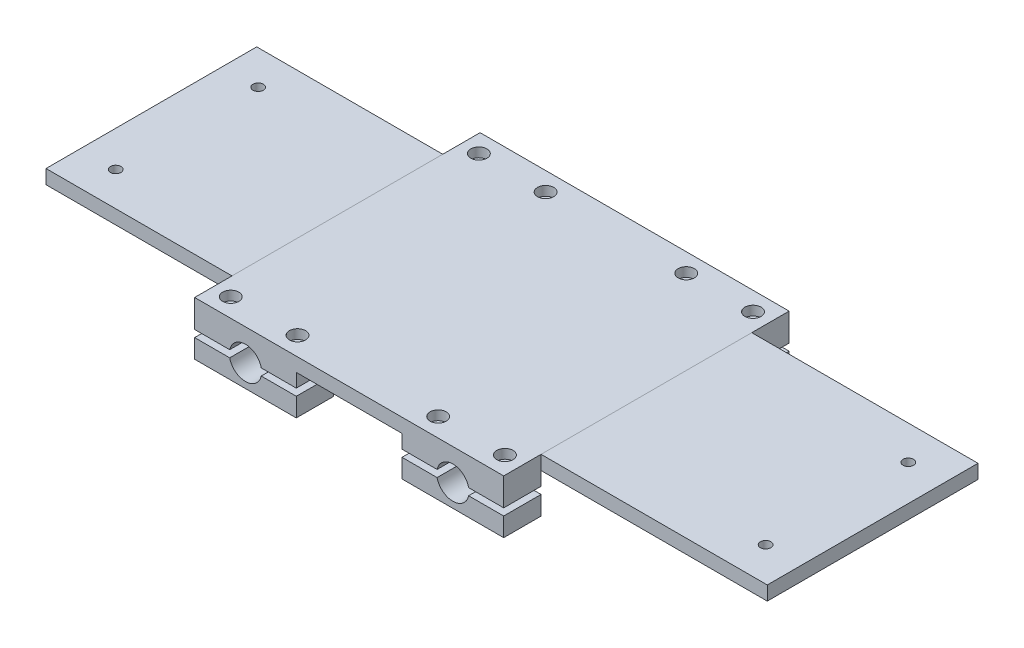
SolidWorks part; units mm, degrees
ref_plane "Front Plane" through (0, 0, 0) normal (0, 0, 1) x (1, 0, 0)
ref_plane "Top Plane" through (0, 0, 0) normal (0, 1, 0) x (1, 0, 0)
ref_plane "Right Plane" through (0, 0, 0) normal (1, 0, 0) x (0, 0, -1)
sketch "Sketch1" plane through (0, 0, 0) normal (0, 0, 1) x (1, 0, 0)
  line L0 (73.8188, 0) -> (0, 0) construction
  line L1 (-110, -15.875) -> (110, -15.875)
  line L2 (-110, -15.875) -> (-110, 15.875)
  line L3 (-110, 15.875) -> (110, 15.875)
  line L4 (110, -15.875) -> (110, 15.875)
  line L5 (-110, -15.875) -> (110, 15.875) construction
  line L6 (-110, 15.875) -> (110, -15.875) construction
  line L7 (0, 0) -> (-73.8187, 0) construction
  circle A1 centre (-73.8187, 0) radius 11.5
  circle A2 centre (73.8188, 0) radius 11.5
  point P0 (0, 0)
  dimension "D1" = 147.6375
  dimension "D4" = 23
  dimension "D2" = 31.75
  dimension "D3" = 220
extrude "Boss-Extrude1" add sketch "Sketch1" along normal blind 203.2
sketch "Sketch3" plane through (0, 0, 203.2) normal (0, 0, 1) x (1, 0, 0)
  line L0 (110, -15.875) -> (110, 15.875) construction
  line L1 (-110, 15.875) -> (110, 15.875)
  line L2 (-110, 15.875) -> (-110, 22.225)
  line L3 (-110, 22.225) -> (110, 22.225)
  line L4 (110, 15.875) -> (110, 22.225)
  dimension "D1" = 6.35
extrude "Boss-Extrude2" add sketch "Sketch3" against normal up to surface (203.2 mm away) up to face at (-62.3188, 0, 0)
sketch "Sketch4" plane through (-110, 0, 0) normal (-1, 0, 0) x (0, 0, 1)
  line L0 (203.2, -15.875) -> (0, -15.875) construction
  line L1 (26.6, -15.875) -> (176.6, -15.875)
  line L2 (26.6, -15.875) -> (26.6, 12.225)
  line L3 (26.6, 12.225) -> (176.6, 12.225)
  line L4 (176.6, -15.875) -> (176.6, 12.225)
  line L5 (0, 0) -> (26.6, 0) construction
  line L6 (26.6, 0) -> (176.6, 0) construction
  line L7 (176.6, 0) -> (203.2, 0) construction
  line L8 (203.2, 22.225) -> (203.2, -15.875) construction
  line L9 (0, 22.225) -> (203.2, 22.225) construction
  dimension "D1" = 10
  dimension "D2" = 150
extrude "Cut-Extrude1" cut sketch "Sketch4" against normal blind 253.2
sketch "Sketch5" plane through (0, 0, 0) normal (0, 0, -1) x (-1, 0, 0)
  line L0 (110, -15.875) -> (-110, -15.875) construction
  line L1 (-37.6375, -15.875) -> (37.6375, -15.875)
  line L2 (-37.6375, -15.875) -> (-37.6375, 12.225)
  line L3 (-37.6375, 12.225) -> (37.6375, 12.225)
  line L4 (37.6375, -15.875) -> (37.6375, 12.225)
  line L5 (-110, 22.225) -> (110, 22.225) construction
  line L6 (0, 0) -> (-37.6375, 0) construction
  line L7 (0, 0) -> (37.6375, 0) construction
  line L8 (-37.6375, 0) -> (-73.8188, 0) construction
  line L9 (-73.8188, 0) -> (-110, 0) construction
  line L10 (-110, -15.875) -> (-110, 22.225) construction
  dimension "D1" = 10
extrude "Cut-Extrude2" cut sketch "Sketch5" against normal blind 203.2
sketch "Sketch6" plane through (0, -15.875, 0) normal (0, -1, 0) x (1, 0, 0)
  line L0 (-110, 189.9) -> (-97.5688, 189.9) construction
  line L2 (-97.5688, 189.9) -> (-50.0688, 189.9) construction
  line L3 (-50.0688, 189.9) -> (-37.6375, 189.9) construction
  line L5 (-110, 13.3) -> (-97.5688, 13.3) construction
  line L6 (-110, 26.6) -> (-110, 0) construction
  line L7 (-97.5688, 13.3) -> (-50.0688, 13.3) construction
  line L8 (-50.0688, 13.3) -> (-37.6375, 13.3) construction
  line L9 (-37.6375, 26.6) -> (-37.6375, 0) construction
  line L10 (37.6375, 203.2) -> (37.6375, 176.6) construction
  line L11 (37.6375, 26.6) -> (37.6375, 0) construction
  line L12 (37.6375, 13.3) -> (50.0688, 13.3) construction
  line L13 (50.0688, 13.3) -> (97.5687, 13.3) construction
  line L14 (97.5687, 13.3) -> (110, 13.3) construction
  line L16 (-62.3188, 203.2) -> (-85.3187, 203.2) construction
  line L18 (110, 189.9) -> (97.5687, 189.9) construction
  line L19 (97.5687, 189.9) -> (50.0688, 189.9) construction
  line L20 (50.0688, 189.9) -> (37.6375, 189.9) construction
  line L22 (-62.3188, 203.2) -> (-85.3187, 203.2)
  line L23 (-85.3187, 203.2) -> (-85.3187, 0) construction
  line L24 (-110, 0) -> (-37.6375, 0) construction
  line L25 (-62.3188, 203.2) -> (-62.3188, 0) construction
  line L28 (-37.6375, 203.2) -> (-37.6375, 176.6) construction
  line L29 (-110, 203.2) -> (-110, 176.6) construction
  line L30 (110, 203.2) -> (110, 176.6) construction
  circle A0 centre (-50.0688, 189.9) radius 3.7258
  circle A1 centre (-97.5688, 189.9) radius 3.7258
  circle A2 centre (-97.5688, 13.3) radius 3.7258
  circle A3 centre (-50.0688, 13.3) radius 3.7258
  circle A4 centre (50.0688, 13.3) radius 3.7258
  circle A5 centre (97.5687, 13.3) radius 3.7258
  circle A6 centre (97.5687, 189.9) radius 3.7258
  circle A7 centre (50.0688, 189.9) radius 3.7258
  dimension "D1" = 7.4516
  dimension "D2" = 47.5
extrude "Cut-Extrude3" cut sketch "Sketch6" against normal blind 203.2 contours A4 | A5 | A3 | A2 | A1 | A0 | A7 | A6
sketch "Sketch7" plane through (0, 0, 0) normal (0, 0, -1) x (-1, 0, 0)
  line L0 (-110, -15.875) -> (-110, 22.225) construction
  line L1 (110, -2.5) -> (-110, -2.5)
  line L2 (110, -2.5) -> (110, 2.5)
  line L3 (110, 2.5) -> (-110, 2.5)
  line L4 (-110, -2.5) -> (-110, 2.5)
  line L5 (110, -2.5) -> (-110, 2.5) construction
  line L6 (110, 2.5) -> (-110, -2.5) construction
  point P0 (0, 0)
  dimension "D1" = 5
extrude "Cut-Extrude4" cut sketch "Sketch7" against normal blind 203.2
sketch "Sketch8" plane through (-110, 0, 0) normal (-1, 0, 0) x (0, 0, 1)
  line L0 (176.6, 12.225) -> (26.6, 12.225) construction
  line L1 (176.6, 12.225) -> (26.6, 12.225)
  line L2 (176.6, 12.225) -> (176.6, 22.225)
  line L3 (176.6, 22.225) -> (26.6, 22.225)
  line L4 (26.6, 12.225) -> (26.6, 22.225)
  line L5 (0, 22.225) -> (203.2, 22.225) construction
  line M4 (26.6, 12.225) -> (176.6, 12.225)
  line M8 (203.2, 22.225) -> (0, 22.225)
extrude "Boss-Extrude3" add sketch "Sketch8" along normal blind 132.4137 contours L4 L2 M4 M8 region at (-110, 17.225, 101.6)
sketch "Sketch9" plane through (110, 0, 0) normal (1, 0, 0) x (0, 0, -1)
  line L0 (-176.6, 12.225) -> (-26.6, 12.225) construction
  line L1 (-176.6, 12.225) -> (-26.6, 12.225)
  line L2 (-176.6, 12.225) -> (-176.6, 22.225)
  line L3 (-176.6, 22.225) -> (-26.6, 22.225)
  line L4 (-26.6, 12.225) -> (-26.6, 22.225)
  line L5 (0, 22.225) -> (-203.2, 22.225) construction
extrude "Boss-Extrude4" add sketch "Sketch9" along normal blind 161.0473
ref_plane "Plane1" through (-110, 0, 0) normal (-1, 0, 0) x (0, 0, 1)
ref_plane "Plane2" through (110, 0, 0) normal (1, 0, 0) x (0, 0, -1)
split line "Split Line1"
split line "Split Line2"
sketch "Sketch10" plane through (0, 22.225, 0) normal (0, 1, 0) x (1, 0, 0)
  line L1 (0, 0) -> (0, -203.2) construction
  line L3 (110, 0) -> (-110, 0) construction
  line L4 (110, -203.2) -> (-110, -203.2) construction
  line L5 (-217.0137, -152.4) -> (245.6473, -152.4) construction
  circle A8 centre (-217.0137, -152.4) radius 3.7258
  circle A9 centre (-217.0137, -50.9667) radius 3.7258
  circle A10 centre (245.6473, -50.8) radius 3.7258
  circle A11 centre (245.6473, -152.4) radius 3.7258
  dimension "D1" = 7.4516
extrude "Cut-Extrude5" cut sketch "Sketch10" against normal blind 10
sketch "Sketch11" plane through (0, 22.225, 0) normal (0, 1, 0) x (1, 0, 0)
  circle A0 centre (97.5687, -13.3) radius 5.7625
  circle A1 centre (50.0688, -13.3) radius 5.7625
  circle A2 centre (97.5687, -189.9) radius 5.7625
  circle A3 centre (50.0688, -189.9) radius 5.7625
  circle A4 centre (-50.0688, -189.9) radius 5.7625
  circle A5 centre (-97.5688, -189.9) radius 5.7625
  circle A6 centre (-97.5688, -13.3) radius 5.7625
  circle A7 centre (-50.0688, -13.3) radius 5.7625
  dimension "D1" = 11.525
extrude "Cut-Extrude6" cut sketch "Sketch11" against normal blind 6.6675
